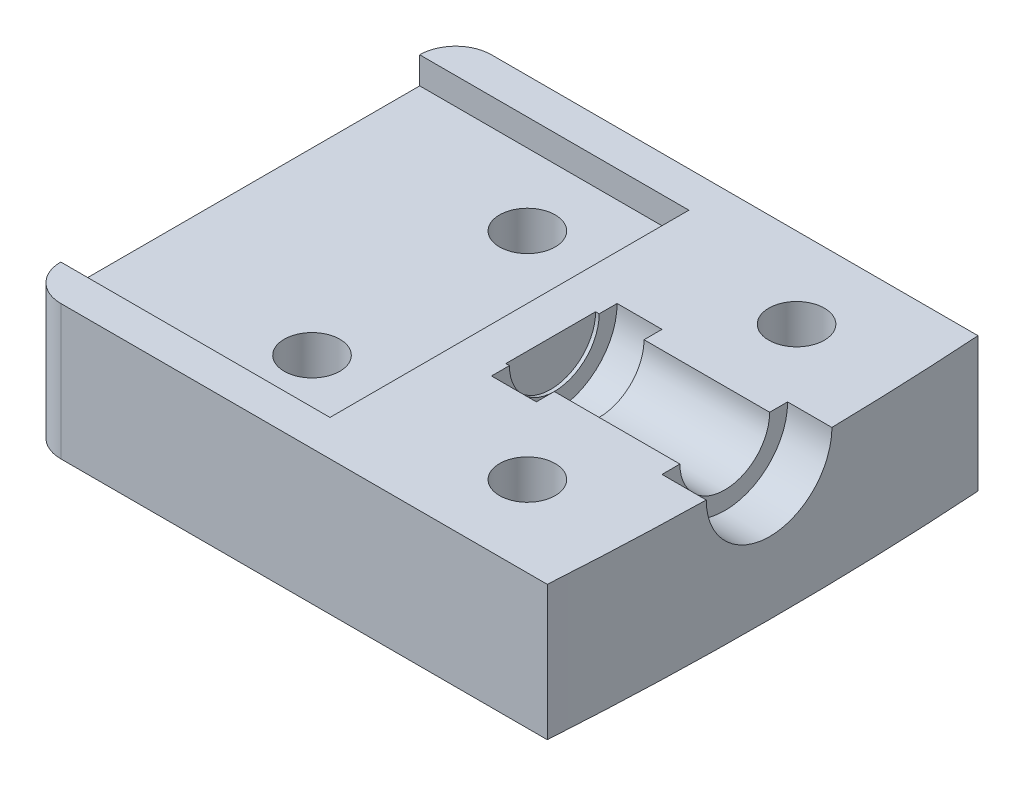
SolidWorks part; units mm, degrees
ref_plane "Front Plane" through (0, 0, 0) normal (0, 0, 1) x (1, 0, 0)
ref_plane "Top Plane" through (0, 0, 0) normal (0, 1, 0) x (1, 0, 0)
ref_plane "Right Plane" through (0, 0, 0) normal (1, 0, 0) x (0, 0, -1)
sketch "Sketch1" plane through (0, 0, 0) normal (0, 1, 0) x (1, 0, 0)
  line L0 (0, 0) -> (-180, 0) construction
  line L1 (0, -12) -> (-25, -12)
  line L2 (0, -12) -> (0, 12)
  line L3 (0, 12) -> (-25, 12)
  line L4 (-25, -12) -> (-25, 12)
  line L5 (-180, 0) -> (4.5, 0) construction
  line L6 (0, 12) -> (4.1093, 12)
  line L7 (0, -12) -> (4.1093, -12)
  line L8 (-180, 0) -> (5, 0) construction
  arc A0 (4.1093, -12) -> (4.1093, 12) centre (-180, 0) ccw
  circle A1 centre (-180, 0) radius 185 construction
  point P4 (0, 0)
  dimension "D4" = 184.5
  dimension "D5" = 185
  dimension "D1" = 25
  dimension "D2" = 24
  dimension "D3" = 180
extrude "Boss-Extrude1" add sketch "Sketch1" along normal blind 10 contours L4 L1 L2 L3 | L7 A0 L6 L2 region at (-12.5, 0, 0) region at (2.1865, 0, 0)
sketch "Sketch2" plane through (0, 10, 0) normal (0, 1, 0) x (1, 0, 0)
  line L1 (-25, -12) -> (-25, 12) construction
  line L2 (-25, 10) -> (-10, 10)
  line L3 (-25, 10) -> (-25, -10)
  line L4 (-25, -10) -> (-10, -10)
  line L5 (-10, 10) -> (-10, -10)
  point P0 (-25, 0)
  point P7 (-25, 0)
  dimension "D1" = 20
  dimension "D2" = 15
extrude "Cut-Extrude1" cut sketch "Sketch2" against normal blind 1.5
sketch "Sketch3" plane through (0, 10, 0) normal (0, 1, 0) x (1, 0, 0)
  line L0 (5, 0) -> (-7.5, 0) construction
  line L1 (0, 0) -> (-180, 0) construction
  dimension "D1" = 12.5
ref_plane "shaft" through (-7.5, 0, 0) normal (1, 0, 0) x (0, 0, -1)
sketch "Sketch4" plane through (-7.5, 0, 0) normal (1, 0, 0) x (0, 0, -1)
  line L0 (12, 10) -> (-12, 10) construction
  circle A0 centre (0, 10) radius 2.1
  dimension "D1" = 4.2
extrude "Cut-Extrude2" cut sketch "Sketch4" along normal through all
fillet "Fillet1" radius 2 2 edges at (-25, 5, -12) (-25, 5, 12)
sketch "Sketch5" plane through (-7.5, 0, 0) normal (1, 0, 0) x (0, 0, -1)
  line L0 (-2.1, 10) -> (2.1, 10) construction
  circle A0 centre (0, 10) radius 3.5
  dimension "D1" = 7
extrude "Cut-Extrude3" cut sketch "Sketch5" along normal blind 2.5
sketch "Sketch7" plane through (-7.5, 0, 0) normal (1, 0, 0) x (0, 0, -1)
  line L0 (-3.5, 10) -> (3.5, 10) construction
  circle A0 centre (0, 10) radius 2.5
  dimension "D1" = 5
extrude "Cut-Extrude4" cut sketch "Sketch7" against normal blind 0.2 and the other way blind 2.7
ref_plane "Plane2" through (0, 10, 0) normal (0, 1, 0) x (1, 0, 0)
sketch "Sketch8" plane through (0, 10, 0) normal (0, 1, 0) x (1, 0, 0)
  line L0 (0, 0) -> (4.5, 0) construction
  line L2 (2, 0) -> (4.5, 0)
  line L3 (2, 0) -> (2, 3.5)
  line L4 (2, 3.5) -> (4.5, 3.5)
  line L5 (4.5, 0) -> (4.5, 3.5)
  arc A0 (4.488, -2.1) -> (4.488, 2.1) centre (-180, 0) ccw construction
  dimension "D1" = 2.5
  dimension "D2" = 7
revolve "Cut-Revolve1" cut sketch "Sketch8" angle 360 about L0
sketch "Sketch9" plane through (2, 0, 0) normal (1, 0, 0) x (0, 0, -1)
  circle A0 centre (0, 10) radius 2.5
  dimension "D1" = 5
extrude "Cut-Extrude5" cut sketch "Sketch9" against normal up to surface (9.7 mm away) up to face at (-7.7, 8.75, 0)
sketch "Sketch11" plane through (0, 8.5, 0) normal (0, 1, 0) x (1, 0, 0)
  circle A0 centre (-15, -6) radius 1.5 construction
  circle A1 centre (-15, 6) radius 1.5 construction
  circle A2 centre (-15, -6) radius 1.5 construction
  circle A3 centre (-15, 6) radius 1.5 construction
hole_wizard "Ø3.1 (3.1) Diameter Hole1" positions "Sketch12" profile "Sketch13" hole size "Ø3.1" standard "ISO" end condition through all
sketch "Sketch12" plane through (0, 8.5, 0) normal (0, 1, 0) x (1, 0, 0)
  point P0 (-15, 6)
  point P3 (-15, -6)
sketch "Sketch13" plane through (-15, 8.5, -6) normal (1, 0, 0) x (0, 0, 1)
  line L0 (0, 0) -> (0, 8.5)
  line L1 (0, 8.5) -> (1.55, 8.5)
  line L2 (1.55, 8.5) -> (1.55, 0)
  line L5 (1.55, 0) -> (0, 0)
  line L11 (0, -6.35) -> (0, 107.95) construction
  dimension "Thru Hole Dia." = 3.1
  dimension "Thru Hole Depth" = 8.5
sketch "Sketch14" plane through (0, 10, 0) normal (0, 1, 0) x (1, 0, 0)
  line L0 (-10, 0) -> (0, 0) construction
  line L1 (-10, -10) -> (-10, 10) construction
  line L2 (-1.5, 12) -> (-1.5, -12) construction
  line L3 (4.1093, 12) -> (-23, 12) construction
  line L4 (4.1093, -12) -> (-23, -12) construction
  point P7 (-1.5, -7.5)
  point P13 (-1.5, 7.5)
  dimension "D1" = 8.5
  dimension "D2" = 15
hole_wizard "Ø3.1 (3.1) Diameter Hole2" positions "Sketch15" profile "Sketch16" hole size "Ø3.1" standard "ISO" end condition through all
sketch "Sketch15" plane through (0, 10, 0) normal (0, 1, 0) x (1, 0, 0)
  point P0 (-1.5, 7.5)
  point P3 (-1.5, -7.5)
sketch "Sketch16" plane through (-1.5, 10, -7.5) normal (1, 0, 0) x (0, 0, 1)
  line L0 (0, 0) -> (0, 10)
  line L1 (0, 10) -> (1.55, 10)
  line L2 (1.55, 10) -> (1.55, 0)
  line L5 (1.55, 0) -> (0, 0)
  line L11 (0, -6.35) -> (0, 107.95) construction
  dimension "Thru Hole Dia." = 3.1
  dimension "Thru Hole Depth" = 10
sketch "Sketch17" plane through (0, 0, 0) normal (0, -1, 0) x (1, 0, 0)
  line L3 (-25, 10) -> (-25, -10)
  line L4 (-23, -12) -> (4.1093, -12)
  line L5 (4.1093, 12) -> (-23, 12)
  line L6 (-25, 10) -> (-25, -10)
  line L7 (-23, -12) -> (4.1093, -12)
  line L8 (4.1093, 12) -> (-23, 12)
  arc A3 (-25, -10) -> (-23, -12) centre (-23, -10) ccw
  arc A4 (4.1093, -12) -> (4.1093, 12) centre (-180, 0) ccw
  arc A5 (-23, 12) -> (-25, 10) centre (-23, 10) ccw
  arc A6 (-25, -10) -> (-23, -12) centre (-23, -10) ccw
  arc A7 (4.1093, -12) -> (4.1093, 12) centre (-180, 0) ccw
  arc A8 (-23, 12) -> (-25, 10) centre (-23, 10) ccw
  dimension "D1" = 0
extrude "Cut-Extrude6" cut sketch "Sketch17" against normal blind 2.5
